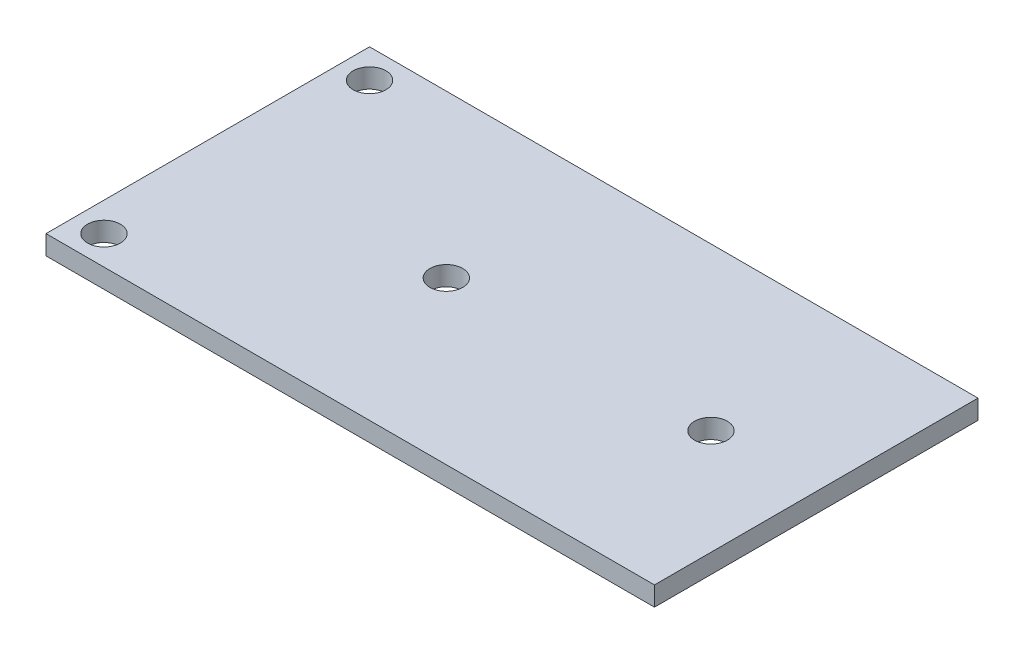
SolidWorks part; units mm, degrees
ref_plane "Front Plane" through (0, 0, 0) normal (0, 0, 1) x (1, 0, 0)
ref_plane "Top Plane" through (0, 0, 0) normal (0, 1, 0) x (1, 0, 0)
ref_plane "Right Plane" through (0, 0, 0) normal (1, 0, 0) x (0, 0, -1)
sketch "Sketch1" plane through (0, 0, 0) normal (0, 1, 0) x (1, 0, 0)
  line L1 (-72.1861, 30.4945) -> (-9.1861, 30.4945)
  line L2 (-72.1861, 30.4945) -> (-72.1861, -3.0055)
  line L3 (-72.1861, -3.0055) -> (-9.1861, -3.0055)
  line L4 (-9.1861, 30.4945) -> (-9.1861, -3.0055)
  dimension "D1" = 63
  dimension "D2" = 33.5
extrude "Boss-Extrude1" add sketch "Sketch1" along normal blind 2
hole_wizard "M3 Clearance Hole1" positions "Sketch3" profile "Sketch2" hole size "M3" standard "ANSI Metric" end condition through all
sketch "Sketch3" plane through (0, 2, 0) normal (0, 1, 0) x (1, 0, 0)
  line L3 (-69.1861, -0.0055) -> (-69.1861, 27.4945) construction
  line L4 (-9.1861, -3.0055) -> (-9.1861, 30.4945) construction
  line L5 (-72.1861, -3.0055) -> (-9.1861, -3.0055) construction
  point P0 (-69.1861, 27.4945)
  point P2 (-69.1861, -0.0055)
  point P15 (-69.1861, 13.7445)
  dimension "D1" = 60
  dimension "D2" = 16.75
  dimension "D3" = 27.5
sketch "Sketch2" plane through (-69.1861, 2, -27.4945) normal (1, 0, 0) x (0, 0, 1)
  line L0 (0, 0) -> (0, 2)
  line L1 (0, 2) -> (1.7, 2)
  line L2 (1.7, 2) -> (1.7, 0)
  line L5 (1.7, 0) -> (0, 0)
  line L11 (0, -6.35) -> (0, 107.95) construction
  dimension "Thru Hole Dia." = 3.4
  dimension "Thru Hole Depth" = 2
hole_wizard "M3 Clearance Hole2" positions "3DSketch1" profile "Sketch5" hole size "M3" standard "ANSI Metric" end condition through all
sketch3d "3DSketch1"
  line L0 (-72.1861, 2, -30.4945) -> (-72.1861, 2, 3.0055) construction
  line L1 (-72.1861, 2, 3.0055) -> (-9.1861, 2, 3.0055) construction
  point P0 (-47.4861, 2, -13.7445)
  point P2 (-20.0861, 2, -13.7445)
  dimension "D1" = 24.7
  dimension "D2" = 27.4
  dimension "D3" = 16.75
sketch "Sketch5" plane through (-47.4861, 2, -13.7445) normal (1, 0, 0) x (0, 0, 1)
  line L0 (0, 0) -> (0, 2)
  line L1 (0, 2) -> (1.7, 2)
  line L2 (1.7, 2) -> (1.7, 0)
  line L5 (1.7, 0) -> (0, 0)
  line L11 (0, -6.35) -> (0, 107.95) construction
  dimension "Thru Hole Dia." = 3.4
  dimension "Thru Hole Depth" = 2
